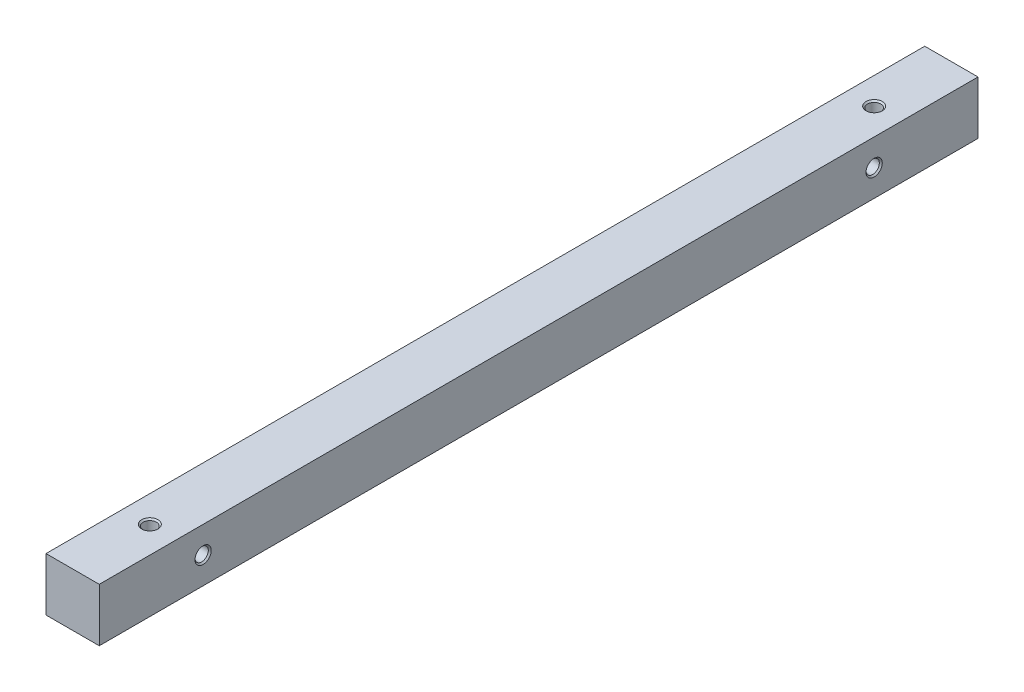
SolidWorks part; units mm, degrees
ref_plane "Plan de face" through (0, 0, 0) normal (0, 0, 1) x (1, 0, 0)
ref_plane "Plan de dessus" through (0, 0, 0) normal (0, 1, 0) x (1, 0, 0)
ref_plane "Plan de droite" through (0, 0, 0) normal (1, 0, 0) x (0, 0, -1)
sketch "Esquisse1" plane through (0, 0, 0) normal (0, 0, 1) x (1, 0, 0)
  line L0 (-5, 5) -> (5, -5) construction
  line L1 (-5, 5) -> (5, 5)
  line L2 (-5, 5) -> (-5, -5)
  line L3 (-5, -5) -> (5, -5)
  line L4 (5, 5) -> (5, -5)
  dimension "D1" = 10
extrude "Boss.-Extru.1" add sketch "Esquisse1" along normal mid plane 165
hole_wizard "Trou taraudé M3x0.51" positions "Esquisse3" profile "Esquisse2" tap size "M3x0.5" standard "Ansi Metric" end condition through all
sketch "Esquisse3" plane through (5, 0, 0) normal (1, 0, 0) x (0, 0, -1)
  point P0 (63, 0)
  point P3 (-63, 0)
sketch "Esquisse2" plane through (5, 0, -63) normal (0, 1, 0) x (0, 0, -1)
  line L0 (0, 0) -> (0, 10)
  line L1 (0, 10) -> (1.25, 10)
  line L2 (1.25, 10) -> (1.25, 0.275)
  line L3 (1.25, 0.275) -> (1.525, 0)
  line L5 (1.525, 0) -> (0, 0)
  line L6 (-1.25, 0.275) -> (-1.525, 0) construction
  line L11 (0, -6.35) -> (0, 107.95) construction
  dimension "Diamètre du trou pour taraudage jusqu'au prochain" = 2.5
  dimension "Profondeur du trou pour taraudage jusqu'au prochain" = 10
  dimension "Diamètre du fraisage entrant" = 3.05
  dimension "Angle du fraisage entrant" = 90
cosmetic thread "Filetage de perçage1"
cosmetic thread "Filetage de perçage2"
hole_wizard "Trou taraudé M3x0.52" positions "Esquisse5" profile "Esquisse4" tap size "M3x0.5" standard "Ansi Metric" end condition through all
sketch "Esquisse5" plane through (0, 5, 0) normal (0, 1, 0) x (1, 0, 0)
  line L0 (0, 0) -> (-36.1539, 0) construction
  line L2 (5, 82.5) -> (-5, 82.5) construction
  point P0 (0, 68)
  point P2 (0, -68)
  dimension "D1" = 68
  dimension "D2" = 14.5
sketch "Esquisse4" plane through (0, 5, -68) normal (1, 0, 0) x (0, 0, 1)
  line L0 (0, 0) -> (0, 10)
  line L1 (0, 10) -> (1.25, 10)
  line L2 (1.25, 10) -> (1.25, 0.275)
  line L3 (1.25, 0.275) -> (1.525, 0)
  line L5 (1.525, 0) -> (0, 0)
  line L6 (-1.25, 0.275) -> (-1.525, 0) construction
  line L11 (0, -6.35) -> (0, 107.95) construction
  dimension "Diamètre du trou pour taraudage jusqu'au prochain" = 2.5
  dimension "Profondeur du trou pour taraudage jusqu'au prochain" = 10
  dimension "Diamètre du fraisage entrant" = 3.05
  dimension "Angle du fraisage entrant" = 90
cosmetic thread "Filetage de perçage3"
cosmetic thread "Filetage de perçage4"
